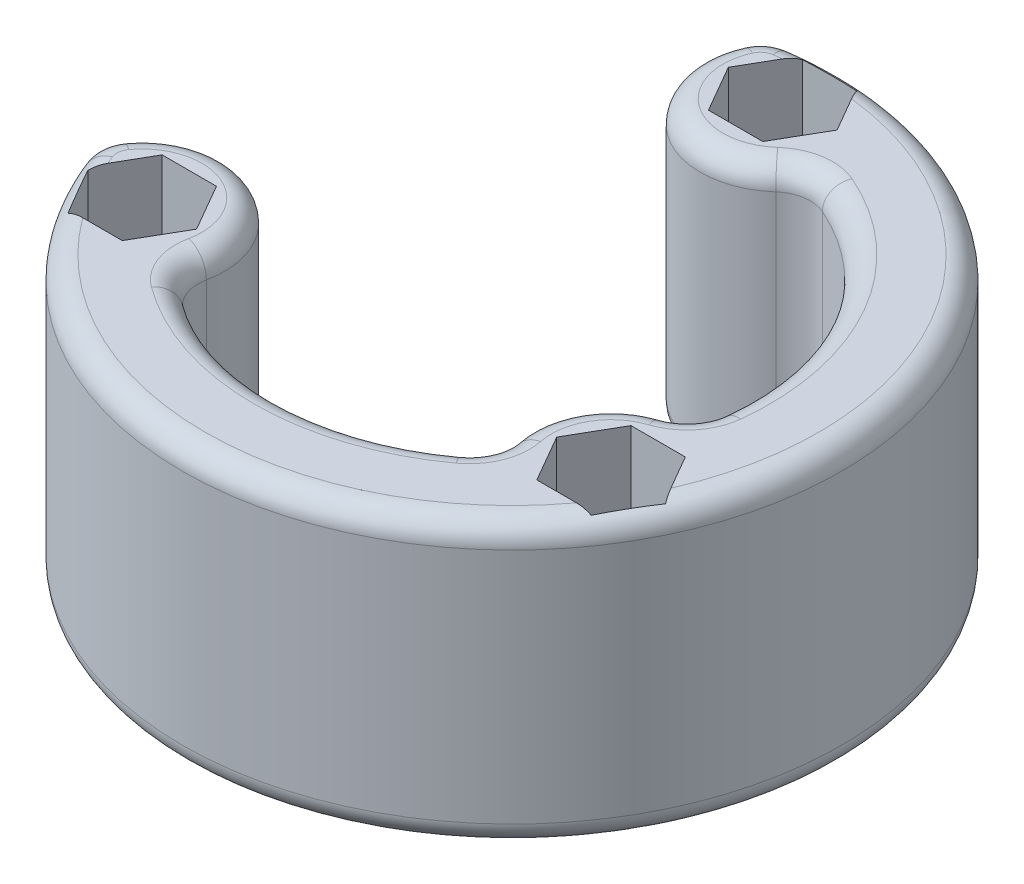
SolidWorks part; units mm, degrees
material "6061-T6 (SS)"
ref_plane "Front Plane" through (0, 0, 0) normal (0, 0, 1) x (1, 0, 0)
ref_plane "Top Plane" through (0, 0, 0) normal (0, 1, 0) x (1, 0, 0)
ref_plane "Right Plane" through (0, 0, 0) normal (1, 0, 0) x (0, 0, -1)
sketch "Sketch1" plane through (0, 0, 0) normal (0, 1, 0) x (1, 0, 0)
  line L0 (0, 12.7) -> (0, 22.225) construction
  line L1 (3.6662, 18.2562) -> (1.8331, 21.4312)
  line L2 (1.8331, 21.4312) -> (-1.8331, 21.4312)
  line L3 (-1.8331, 21.4312) -> (-3.6662, 18.2562)
  line L4 (-3.6662, 18.2562) -> (-1.8331, 15.0812)
  line L5 (-1.8331, 15.0812) -> (1.8331, 15.0812)
  line L6 (1.8331, 15.0812) -> (3.6662, 18.2562)
  line L7 (13.9773, -5.9531) -> (12.1442, -9.1281)
  line L8 (17.6435, -5.9531) -> (13.9773, -5.9531)
  line L9 (12.1442, -9.1281) -> (13.9773, -12.3031)
  line L10 (13.9773, -12.3031) -> (17.6435, -12.3031)
  line L11 (17.6435, -12.3031) -> (19.4766, -9.1281)
  line L12 (19.4766, -9.1281) -> (17.6435, -5.9531)
  line L13 (-12.1442, -9.1281) -> (-13.9773, -5.9531)
  line L14 (-13.9773, -12.3031) -> (-12.1442, -9.1281)
  line L15 (-13.9773, -5.9531) -> (-17.6435, -5.9531)
  line L16 (-17.6435, -5.9531) -> (-19.4766, -9.1281)
  line L17 (-19.4766, -9.1281) -> (-17.6435, -12.3031)
  line L18 (-17.6435, -12.3031) -> (-13.9773, -12.3031)
  line L23 (0, 0) -> (15.8104, -9.1281) construction
  line L24 (0, 0) -> (-15.8104, -9.1281) construction
  arc A0 (-21.024, -7.2071) -> (-4.2704, 21.8109) centre (0, 0) ccw
  circle A1 centre (0, 0) radius 12.7 construction
  circle A2 centre (0, 18.2562) radius 3.175 construction
  circle A3 centre (15.8104, -9.1281) radius 3.175 construction
  circle A4 centre (-15.8104, -9.1281) radius 3.175 construction
  arc A5 (10.8353, -11.6022) -> (-10.8353, -11.6022) centre (0, 0) cw
  arc A6 (-10.8353, -11.6022) -> (-21.024, -7.2071) centre (-15.8104, -9.1281) ccw
  arc A8 (-4.2704, 21.8109) -> (4.6301, 15.1848) centre (0, 18.2562) ccw
  arc A9 (4.6301, 15.1848) -> (15.4655, -3.5826) centre (0, 0) cw
  arc A10 (15.4655, -3.5826) -> (10.8353, -11.6022) centre (15.8104, -9.1281) ccw
  point P33 (-19.0123, -8.6818)
  point P34 (13.7236, -9.6974)
  point P36 (-21.0724, -7.0642)
  point P39 (11.6795, 13.0372)
  point P42 (3.5094, 12.3607)
  point P43 (-3.3211, 12.2581)
  point P44 (0, 0)
  point P45 (12.7009, -13.7328)
  point P46 (-4.2562, 21.8137)
  dimension "D1" = 6.35
  dimension "D2" = 25.4
  dimension "D3" = 44.45
  dimension "D6" = 6.35
  dimension "D4" = 3.9688
  dimension "D5" = 3
extrude "Boss-Extrude1" add sketch "Sketch1" along normal blind 19.05
fillet "Fillet1" radius 2.54 6 edges at (4.6301, 9.525, -15.1848) (10.8353, 9.525, 11.6022) (15.4655, 9.525, 3.5826) (-10.8353, 9.525, 11.6022) (-21.024, 9.525, 7.2071) (-4.2704, 9.525, -21.8109)
fillet "Fillet2" radius 1.524 24 edges at (-3.2881, 0, -13.7774) (4.9829, 0, -14.7123) (13.7482, 0, -7.9375) (15.2327, 0, 3.0409) (10.9985, 0, 6.35) (10.2498, 0, 11.6715) (0, 0, 15.875) (-10.2498, 0, 11.6715) (-13.5756, 0, 4.0411) (-3.2881, 19.05, -13.7774) (4.9829, 19.05, -14.7123) (13.7482, 19.05, -7.9375) (15.2327, 19.05, 3.0409) (10.9985, 19.05, 6.35) (10.2498, 19.05, 11.6715) (0, 19.05, 15.875) (-10.2498, 19.05, 11.6715) (-13.5756, 19.05, 4.0411) (19.2474, 0, 11.1125) (19.2474, 19.05, 11.1125) (-20.7776, 0, 7.0566) (-4.2776, 0, -21.5222) (-20.7776, 19.05, 7.0566) (-4.2776, 19.05, -21.5222)
